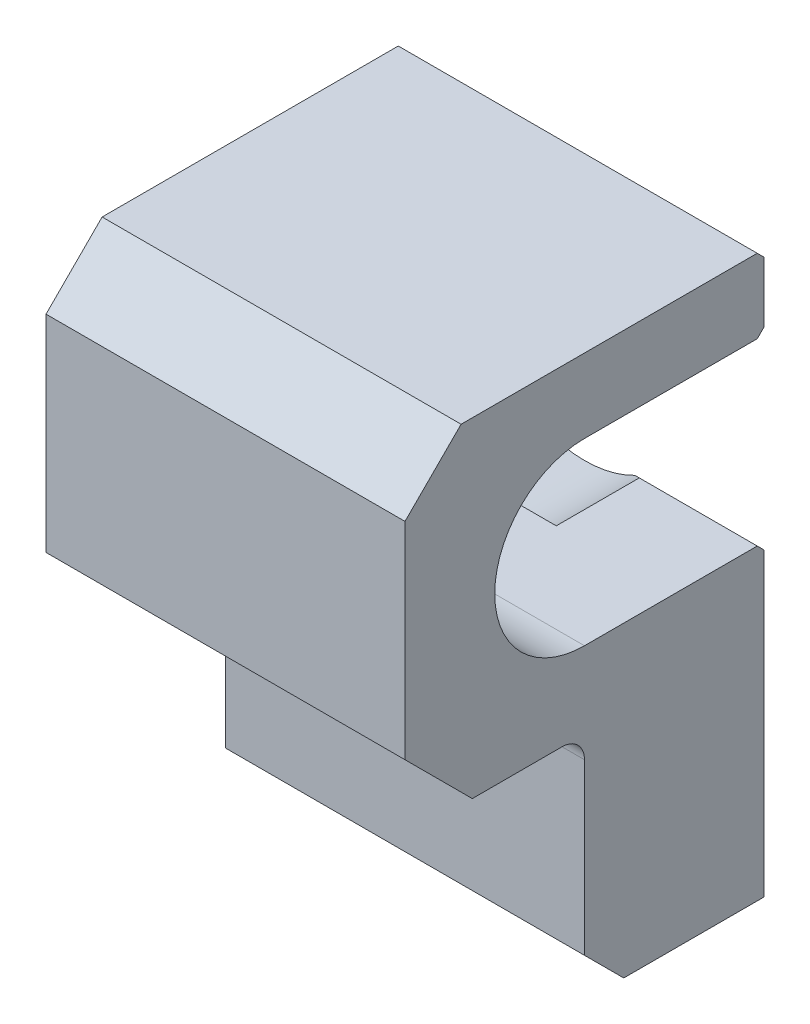
SolidWorks part; units mm, degrees
material "AISI 304"
ref_plane "Front Plane" through (0, 0, 0) normal (0, 0, 1) x (1, 0, 0)
ref_plane "Top Plane" through (0, 0, 0) normal (0, 1, 0) x (1, 0, 0)
ref_plane "Right Plane" through (0, 0, 0) normal (1, 0, 0) x (0, 0, -1)
sketch "Sketch2" plane through (0, 0, 0) normal (1, 0, 0) x (0, 0, -1)
  line L0 (0, -0.3) -> (0, -13.7)
  line L1 (0, -13.7) -> (-6.25, -13.7)
  line L2 (-6.25, -13.7) -> (-8, -11.95)
  line L3 (-8, -11.95) -> (-8, -4.4)
  line L4 (-9, -3.4) -> (-13, -3.4)
  line L5 (-13, -3.4) -> (-16, -0.4)
  line L6 (-16, -0.4) -> (-16, 8.8)
  line L7 (-16, 8.8) -> (-13.5, 11.3)
  line L8 (-13.5, 11.3) -> (-0.3, 11.3)
  line L9 (0, 11) -> (0, 8.3)
  line L10 (-0.3, 8) -> (-8, 8)
  line L11 (-0.3, 0) -> (-8, 0)
  line L12 (0, -0.3) -> (-0.3, 0)
  line L13 (0, 8.3) -> (-0.3, 8)
  line L14 (-0.3, 11.3) -> (0, 11)
  arc A0 (-8, 8) -> (-8, 0) centre (-8, 4) ccw
  arc A1 (-8, -4.4) -> (-9, -3.4) centre (-9, -4.4) ccw
  point P0 (0, 0)
  point P11 (0, 11.3)
  point P12 (0, 8)
  dimension "D7" = 1
  dimension "D9" = 4
  dimension "D1" = 13.7
  dimension "D2" = 8
  dimension "D3" = 45
  dimension "D4" = 45
  dimension "D5" = 45
  dimension "D6" = 6.25
  dimension "D8" = 25
  dimension "D10" = 8
  dimension "D11" = 8
  dimension "D12" = 8
  dimension "D13" = 5
  dimension "D14" = 14.7
  dimension "D15" = 3.3
  dimension "D16" = 3.4
  dimension "D17" = 13.5
  dimension "D18" = 9.2
extrude "Boss-Extrude1" add sketch "Sketch2" along normal blind 8 and the other way blind 8
sketch "Sketch3" plane through (0, 0, 0) normal (0, 0, -1) x (-1, 0, 0)
  line L0 (0, 0) -> (0, 8) construction
  line L1 (8, 8) -> (-8, 8) construction
  circle A0 centre (0, 4) radius 4.85
  dimension "D1" = 9.7
extrude "Cut-Extrude1" cut sketch "Sketch3" against normal blind 4
sketch "Sketch6" plane through (0, 0, 0) normal (0, 0, -1) x (-1, 0, 0)
  line L0 (0, -13.7) -> (0, -6.7) construction
  line L1 (8, -13.7) -> (-8, -13.7) construction
  point P1 (0, -6.7)
  point P10 (0, -6.7)
  dimension "D1" = 7
hole_wizard "Tap Drill for 1/4-20 Tap1" positions "Sketch6" profile "Sketch7" hole size "1/4-20" standard "ANSI Inch"
sketch "Sketch7" plane through (0, -6.7, 0) normal (1, 0, 0) x (0, 1, 0)
  line L0 (0, 0) -> (0, 7)
  line L1 (0, 7) -> (2.5527, 5.4662)
  line L2 (2.5527, 5.4662) -> (2.5527, 0)
  line L5 (2.5527, 0) -> (0, 0)
  line L10 (0, 7) -> (-2.5527, 5.4662) construction
  line L11 (0, -6.35) -> (0, 107.95) construction
  dimension "Hole Dia." = 5.1054
  dimension "Hole Depth" = 7
  dimension "Drill Angle" = 118
chamfer "Chamfer1" distance 1 angle 45 1 edges at (0, -4.1473, 0)
thread "Thread1" pitch 1.27 method cut profile "Thread Profile1" start angle 0, offset 2, length 0, pitch 1.27, diameter 5.1054
ref_plane "Plane1" through (2.5527, -6.7, -1) normal (0, -1, 0) x (1, 0, 0)
sketch "Thread Profile1" plane through (2.5527, -6.7, -1) normal (0, -1, 0) x (1, 0, 0)
  line L0 (0, 0) -> (0, 1.27) construction
  line L1 (0, 0) -> (0.6874, 0.3969)
  line L2 (0.6874, 0.3969) -> (0.6874, 0.5556)
  line L3 (0.6874, 0.5556) -> (0, 0.9525)
  line L4 (0.6874, 0.4762) -> (0, 0.4762) construction
  line L11 (0, 0) -> (0, 0.9525)
  point P2 (0, 0)
  dimension "Pitch" = 1.27
  dimension "Profile_Angle" = 60
  dimension "Profile_Land" = 0.1588
  dimension "Profile_Height" = 0.6874
